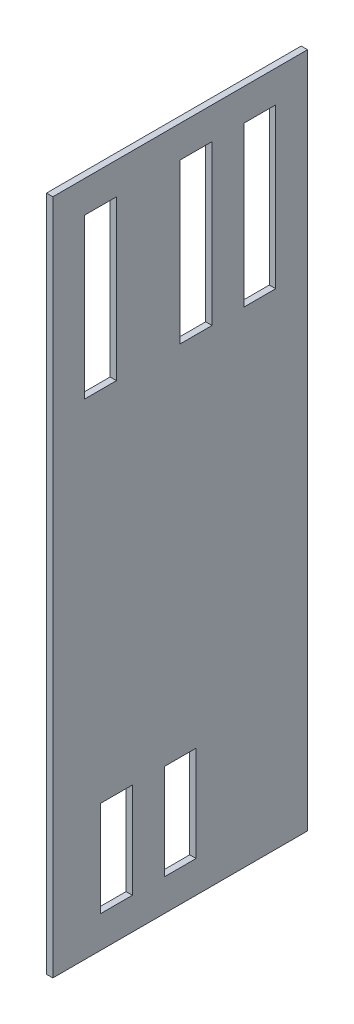
SolidWorks part; units mm, degrees
ref_plane "Front Plane" through (0, 0, 0) normal (0, 0, 1) x (1, 0, 0)
ref_plane "Top Plane" through (0, 0, 0) normal (0, 1, 0) x (1, 0, 0)
ref_plane "Right Plane" through (0, 0, 0) normal (1, 0, 0) x (0, 0, -1)
sketch "Sketch1" plane through (0, 0, 0) normal (1, 0, 0) x (0, 0, -1)
  line L0 (-80, 202.4468) -> (0, 202.4468) construction
  line L1 (0, 0) -> (-80, 0)
  line L2 (0, 0) -> (0, 212.4468)
  line L3 (0, 212.4468) -> (-80, 212.4468)
  line L4 (-80, 0) -> (-80, 212.4468)
  line L5 (-80, 152.4468) -> (0, 152.4468) construction
  line L6 (-80, 40) -> (0, 40) construction
  line L7 (-80, 10) -> (0, 10) construction
  line L9 (-70, 202.4468) -> (-60, 202.4468)
  line L10 (-70, 202.4468) -> (-70, 152.4468)
  line L11 (-70, 152.4468) -> (-60, 152.4468)
  line L12 (-60, 202.4468) -> (-60, 152.4468)
  line L13 (-40, 202.4468) -> (-30, 202.4468)
  line L14 (-40, 202.4468) -> (-40, 152.4468)
  line L15 (-40, 152.4468) -> (-30, 152.4468)
  line L16 (-30, 202.4468) -> (-30, 152.4468)
  line L17 (-20, 202.4468) -> (-10, 202.4468)
  line L18 (-20, 202.4468) -> (-20, 152.4468)
  line L19 (-20, 152.4468) -> (-10, 152.4468)
  line L20 (-10, 202.4468) -> (-10, 152.4468)
  line L21 (-65, 40) -> (-55, 40)
  line L22 (-65, 40) -> (-65, 10)
  line L23 (-65, 10) -> (-55, 10)
  line L24 (-55, 40) -> (-55, 10)
  line L25 (-45, 40) -> (-35, 40)
  line L26 (-45, 40) -> (-45, 10)
  line L27 (-45, 10) -> (-35, 10)
  line L28 (-35, 40) -> (-35, 10)
  point P13 (-40, 40)
  dimension "D1" = 80
  dimension "D2" = 212.4468
  dimension "D3" = 30
  dimension "D4" = 50
  dimension "D5" = 10
  dimension "D6" = 10
  dimension "D7" = 10
  dimension "D8" = 10
  dimension "D9" = 20
  dimension "D10" = 10
  dimension "D11" = 10
  dimension "D12" = 10
  dimension "D13" = 10
  dimension "D14" = 10
  dimension "D15" = 10
  dimension "D16" = 15
base flange "Base-Flange1" sketch "Sketch1" thickness 2 reverse thickness direction no parameters "D1"=0.7366
sketch "Bend-Lines1" [suppressed] plane through (0, 0, 0) normal (0, 1, 0) x (1, 0, 0)
sketch "Bounding-Box1" [suppressed] plane through (0, 0, 0) normal (0, 1, 0) x (1, 0, 0)
sheet metal parameters "Sheet-Metal1" thickness 2 parameters "D1"=0.7366
flat pattern "Flat-Pattern1" [suppressed]
sketch "Bend-Lines2" plane through (0, 0, 0) normal (0, 1, 0) x (1, 0, 0)
sketch3d "Bounding-Box2" [suppressed]
  line L0 (0, 212.4468, 0) -> (0, 0, 0) construction
  line L1 (80, 212.4468, 0) -> (80, 0, 0) construction
  line L2 (0, 212.4468, 0) -> (80, 212.4468, 0) construction
  line L3 (0, 0, 0) -> (80, 0, 0) construction
